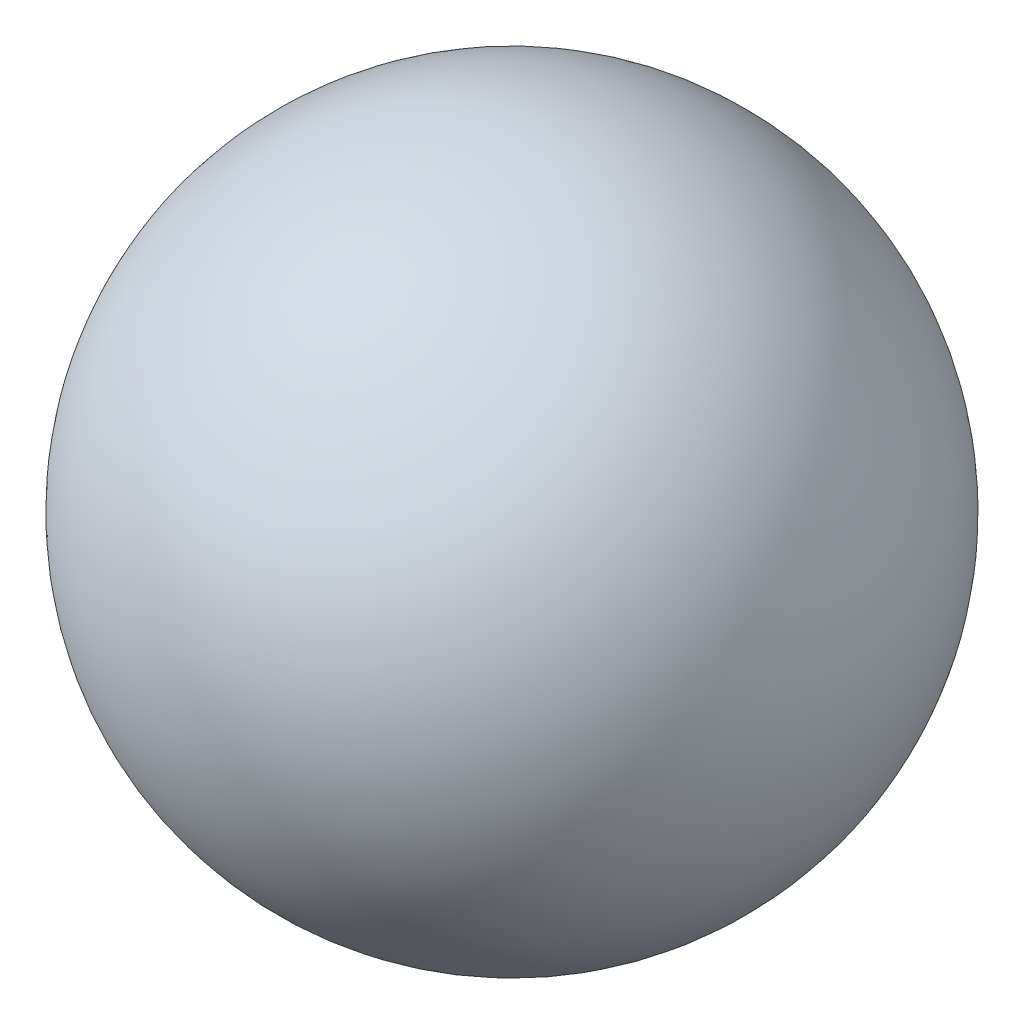
SolidWorks part; units mm, degrees
ref_plane "Front Plane" through (0, 0, 0) normal (0, 0, 1) x (1, 0, 0)
ref_plane "Top Plane" through (0, 0, 0) normal (0, 1, 0) x (1, 0, 0)
ref_plane "Right Plane" through (0, 0, 0) normal (1, 0, 0) x (0, 0, -1)
sketch "Sketch2" plane through (0, 0, 0) normal (0, 0, 1) x (1, 0, 0)
  line L0 (-206.375, 0) -> (206.375, 0) construction
  circle A0 centre (0, 0) radius 206.375
  point P5 (-187.7508, -85.6753)
  point P6 (0, 0)
  dimension "D1" = 412.75
revolve "Revolve3" add sketch "Sketch2" angle 360 about L0 region at (0, 87.5883, 0)
